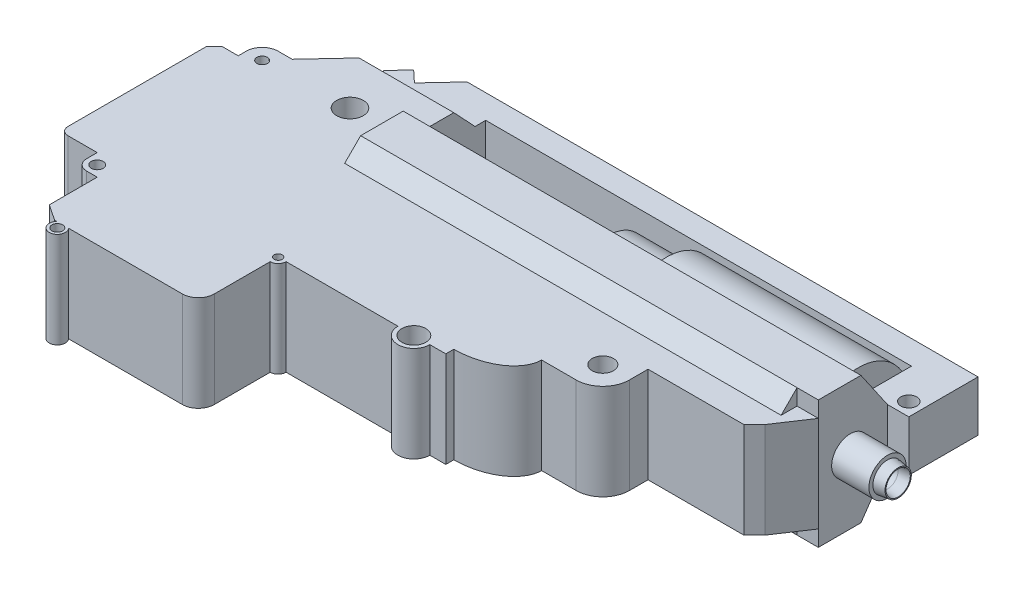
SolidWorks part; units mm, degrees
ref_plane "Alzado" through (0, 0, 0) normal (0, 0, 1) x (1, 0, 0)
ref_plane "Planta" through (0, 0, 0) normal (0, 1, 0) x (1, 0, 0)
ref_plane "Vista lateral" through (0, 0, 0) normal (1, 0, 0) x (0, 0, -1)
sketch "Croquis1" plane through (0, 0, 0) normal (0, 1, 0) x (1, 0, 0)
  line L0 (0, 0) -> (96, 0)
  line L1 (96, 0) -> (96, -13)
  line L2 (0, 0) -> (-4.2707, -4.5758)
  line L3 (96, -13) -> (88, -13)
  line L4 (96, -13) -> (96, -10.5)
  line L5 (96, -10.5) -> (93.5, -10.5)
  line L6 (88, -4.5) -> (88, -13)
  line L7 (88, -4.5) -> (8, -4.5)
  line L8 (88, -13) -> (87.902, -13.0151)
  line L9 (8, -4.5) -> (8, -7.5)
  line L10 (8, -7.5) -> (-7, -7.5)
  line L11 (-7, -7.5) -> (-9.9242, -4.7707)
  line L12 (-9.9242, -4.7707) -> (-7.1949, -1.8465)
  line L13 (-7.1949, -1.8465) -> (-4.2707, -4.5758)
  line L14 (-7, -7.5) -> (-10.4116, -11.1553) construction
  line L15 (-13.3358, -8.426) -> (-10.4116, -11.1553)
  line L16 (-13.1409, -14.0795) -> (-16.0651, -11.3502)
  line L17 (-16.0651, -11.3502) -> (-13.3358, -8.426)
  line L18 (-13.1409, -14.0795) -> (-10.4116, -11.1553)
  circle A0 centre (93.5, -10.5) radius 1.5
  dimension "D7" = 3
  dimension "D1" = 96
  dimension "D2" = 13
  dimension "D3" = 15
  dimension "D4" = 8
  dimension "D5" = 2.5
  dimension "D6" = 2.5
  dimension "D8" = 80
  dimension "D9" = 4
  dimension "D10" = 4
  dimension "D11" = 5
extrude "Saliente-Extruir1" add sketch "Croquis1" along normal blind 9.5 contours A0 L1 L0 L2 L10 L9 L7 L6 L3 | L16 L18 L15 L17 region at (46.9477, 0, 3.2955) region at (-13.2383, 0, 11.2528)
sketch "Croquis2" plane through (88, 0, 0) normal (-1, 0, 0) x (0, 0, 1)
  line L0 (4.5, 4.75) -> (5, 4.75) construction
  line L2 (4.5, 9.5) -> (4.5, 0) construction
  line L3 (5, 4.75) -> (14.5, 4.75) construction
  circle A0 centre (14.5, 4.75) radius 9.5
  dimension "D1" = 0.5
  dimension "D2" = 9.5
extrude "Saliente-Extruir2" add sketch "Croquis2" along normal blind 36
sketch "Croquis3" plane through (52, 0, 0) normal (-1, 0, 0) x (0, 0, 1)
  circle A0 centre (14.5, 4.75) radius 7.5
  dimension "D1" = 15
extrude "Saliente-Extruir3" add sketch "Croquis3" along normal blind 11
sketch "Croquis5" plane through (41, 0, 0) normal (-1, 0, 0) x (0, 0, 1)
  circle A0 centre (14.5, 4.75) radius 3.5
  dimension "D1" = 7
extrude "Saliente-Extruir4" add sketch "Croquis5" along normal blind 33
sketch "Croquis6" plane through (88, 0, 0) normal (1, 0, 0) x (0, 0, -1)
  line L0 (-13, 4.75) -> (-26, 4.75) construction
  line L1 (-13, 9.5) -> (-13, 0) construction
  line L2 (-26, -7.25) -> (-26, 16.75)
  line L3 (-26, 16.75) -> (-18, 16.75)
  line L4 (-18, 16.75) -> (-13, 9.5)
  line L5 (-13, 9.5) -> (-13, 0)
  line L6 (-18, -7.25) -> (-13, 0)
  line L7 (-26, -7.25) -> (-18, -7.25)
  dimension "D1" = 13
  dimension "D2" = 12
  dimension "D3" = 8
extrude "Saliente-Extruir5" add sketch "Croquis6" along normal blind 4
sketch "Croquis7" plane through (92, 0, 0) normal (1, 0, 0) x (0, 0, -1)
  line L0 (-13, 4.75) -> (-20, 4.75) construction
  line L1 (-13, 0) -> (-13, 9.5) construction
  circle A0 centre (-20, 4.75) radius 3.5
  circle A1 centre (-20, 4.75) radius 2
  dimension "D2" = 7
  dimension "D3" = 4
  dimension "D1" = 7
extrude "Saliente-Extruir6" add sketch "Croquis7" along normal blind 7
sketch "Croquis8" plane through (99, 0, 0) normal (1, 0, 0) x (0, 0, -1)
  circle A0 centre (-20, 4.75) radius 2
  circle A1 centre (-20, 4.75) radius 2.75
  dimension "D1" = 5.5
extrude "Saliente-Extruir7" add sketch "Croquis8" along normal blind 2 draft 8
sketch "Croquis9" plane through (8, 0, 0) normal (-1, 0, 0) x (0, 0, 1)
  line L10 (6.5, 9.5) -> (10.5, 13.75)
  line L13 (4.5, 4.75) -> (17.5, 4.75) construction
  line L14 (10.5, 13.75) -> (17.5, 13.75)
  line L15 (17.5, -4.25) -> (17.5, 13.75)
  line L18 (4.5, 0) -> (4.5, 9.5)
  line L19 (4.5, 0) -> (6.5, 0)
  line L20 (4.5, 9.5) -> (10.5, 9.5) construction
  line L21 (17.5, -4.25) -> (10.5, -4.25)
  line L22 (4.5, 9.5) -> (6.5, 9.5)
  line L23 (10.5, 9.5) -> (10.5, 13.75) construction
  line L24 (6.5, 0) -> (10.5, -4.25)
  dimension "D3" = 13
  dimension "D6" = 2
  dimension "D7" = 6
extrude "Saliente-Extruir8" add sketch "Croquis9" along normal blind 23
sketch "Croquis17" plane through (0, 13.75, 0) normal (0, 1, 0) x (1, 0, 0)
  line L0 (0, 0) -> (-16.8, -18)
  line L1 (-16.8, -18) -> (-16.7852, -17.9144)
  line L4 (0, 0) -> (-16.8, 0)
  line L5 (-16.8, 0) -> (-16.8, -18)
  line M3 (8, -10.5) -> (-15, -10.5)
  line M4 (-15, -10.5) -> (-15, -17.5)
extrude "Cortar-Extruir3" cut sketch "Croquis17" along normal blind 40 and the other way blind 34 contours L4 L5 L0 M4 M3 | L0 M3 M4 region at (-10.981, 13.75, 5.3264) region at (-13.2667, 13.75, 12.3571)
sketch "Croquis18" plane through (88, 0, 0) normal (-1, 0, 0) x (0, 0, 1)
  line L0 (18, -7.25) -> (26, -7.25)
  line L1 (26, 16.75) -> (26, -7.25) construction
  line L2 (26, 16.75) -> (18, 16.75)
  line L3 (18, 16.75) -> (18, 13.75)
  line L4 (18, 13.75) -> (26, 13.75)
  line L5 (26, 13.75) -> (29, 13.75)
  line L6 (26, 16.75) -> (29, 13.75)
  line L7 (26, -4.25) -> (29, -4.25)
  line L8 (18, -7.25) -> (18, -4.25)
  line L9 (18, -4.25) -> (26, -4.25)
  line L10 (29, -4.25) -> (26, -7.25)
  dimension "D1" = 3
  dimension "D2" = 3
extrude "Saliente-Extruir10" add sketch "Croquis18" along normal blind 82
sketch "Croquis19" plane through (0, 13.75, 0) normal (0, 1, 0) x (1, 0, 0)
  line L0 (8, -17.5) -> (8, -24.5)
  line L1 (8, -24.5) -> (-26, -24.5)
  line L2 (-26, -24.5) -> (-26, -23)
  line L3 (-26, -23) -> (-24.5, -23) construction
  line L4 (-24.5, -23) -> (-24.5, -21.5) construction
  line L5 (-26, -23) -> (-24.5, -21.5)
  line L6 (-24.5, -21.5) -> (-21.5, -21.5)
  line L7 (-21.5, -21.5) -> (-18.5, -21.5) construction
  line L8 (-18.5, -21.5) -> (-18.5, -20) construction
  line L9 (-18.5, -20) -> (-18.5, -17) construction
  line L10 (-18.5, -17) -> (-16.8667, -17)
  line L11 (8, -17.5) -> (-15, -17.5)
  line L12 (-15, -16.0714) -> (-15.8667, -17)
  line L13 (-15, -16.0714) -> (-15, -17.5)
  line L14 (-21.5, -21.5) -> (-21.5, -20)
  line L15 (-16.8667, -17) -> (-15.8667, -17)
  line L16 (0, 0) -> (0, -19.5) construction
  line L17 (0, -19.5) -> (-2.5, -19.5) construction
  line L20 (-9.8, -10.5) -> (-15, -16.0714)
  line L21 (-15, -16.0714) -> (-15, -17.5)
  line L22 (-15, -17.5) -> (8, -17.5)
  line L23 (8, -17.5) -> (8, -10.5)
  line L24 (8, -10.5) -> (-9.8, -10.5)
  line L25 (-9.8, -10.5) -> (-12.4, -13.2857)
  line L27 (-15, -17.5) -> (8, -17.5)
  line L28 (8, -17.5) -> (8, -10.5)
  line L29 (8, -10.5) -> (-9.8, -10.5)
  arc A0 (-18.5, -17) -> (-21.5, -20) centre (-18.5, -20) ccw
  circle A1 centre (-18.5, -20) radius 1
  line M11 (-15, -16.0714) -> (-15, -17.5)
  line M12 (-15, -17.5) -> (8, -17.5)
  dimension "D11" = 2
  dimension "D1" = 7
  dimension "D2" = 34
  dimension "D3" = 1.5
  dimension "D4" = 1.5
  dimension "D5" = 1.5
  dimension "D6" = 3
  dimension "D7" = 3
  dimension "D8" = 1.5
  dimension "D9" = 3
  dimension "D12" = 19.5
  dimension "D13" = 2.5
  dimension "D10" = 0
extrude "Saliente-Extruir11" add sketch "Croquis19" against normal blind 18 contours L10 A0 L14 L6 L5 L2 L1 L0 M12 M11 region at (-7.6013, 13.75, 21.099)
sketch "Croquis20" plane through (0, 13.75, 0) normal (0, 1, 0) x (1, 0, 0)
  line L0 (0, 0) -> (0, -19.5) construction
  line L1 (0, -19.5) -> (-2.5, -19.5) construction
  circle A0 centre (-2.5, -19.5) radius 2.5
  dimension "D1" = 19.5
  dimension "D2" = 2.5
extrude "Cortar-Extruir4" cut sketch "Croquis20" against normal blind 18
sketch "Croquis21" plane through (0, 13.75, 0) normal (0, 1, 0) x (1, 0, 0)
  line L0 (-26, -24.5) -> (-26, -49)
  line L1 (-24.5, -50.5) -> (-19, -50.5)
  line L2 (-26, -24.5) -> (6, -24.5)
  line L4 (-19, -50.5) -> (-19, -52.5)
  line L5 (-15, -54.5) -> (-15, -63.5)
  line L6 (-15, -63.5) -> (-12, -63.5) construction
  line L7 (-12, -63.5) -> (-12, -65.5) construction
  line L8 (-15, -63.5) -> (-12, -65.5)
  line L9 (-12, -65.5) -> (-11.618, -65.5)
  line L10 (-12, -65.5) -> (-11.618, -65.5)
  line L11 (15, -62.5) -> (15, -52)
  line L12 (-9.382, -65.5) -> (12, -65.5)
  line L14 (16.5, -50.5) -> (37.5, -50.5)
  line L15 (43.5, -50.5) -> (46.5, -50.5)
  line L16 (46.5, -50.5) -> (46.5, -49)
  line L19 (92, -26) -> (88, -32)
  line L20 (88, -32) -> (86, -32) construction
  line L21 (86, -32) -> (86, -34) construction
  line L22 (88, -32) -> (86, -34)
  line L23 (86, -34) -> (68, -34)
  line L24 (96, 0) -> (96, -37.5) construction
  line L25 (-17, -54.5) -> (-15, -54.5)
  line L26 (96, -37.5) -> (63, -37.5) construction
  line L27 (68, -34) -> (68, -37.5)
  line L28 (63, 0) -> (63, -40) construction
  line L29 (0, 0) -> (96, 0) construction
  line L30 (63, -42.5) -> (56.5, -42.5)
  line L31 (6, -24.5) -> (92, -24.5)
  line L32 (92, -18) -> (92, -26) construction
  line L33 (92, -24.5) -> (92, -26)
  arc A0 (-19, -52.5) -> (-17, -54.5) centre (-17, -52.5) ccw
  arc A1 (-11.618, -65.5) -> (-9.382, -65.5) centre (-10.5, -66.5) ccw
  arc A2 (12, -65.5) -> (15, -62.5) centre (12, -62.5) ccw
  arc A3 (15, -52) -> (16.5, -50.5) centre (15, -50.5) ccw
  arc A4 (37.5, -50.5) -> (43.5, -50.5) centre (40.5, -50.5) ccw
  circle A5 centre (63, -37.5) radius 2
  arc A6 (63, -42.5) -> (68, -37.5) centre (63, -37.5) ccw
  circle A7 centre (-10.5, -66.5) radius 0.9991
  circle A8 centre (40.5, -50.5) radius 2.25
  circle A9 centre (15, -50.5) radius 0.75
  circle A10 centre (-17, -52.5) radius 1.1246
  arc A11 (-24.5, -50.5) -> (-26, -49) centre (-24.5, -49) cw
  ellipse E0 centre (46.5, -42.5) end of major axis (56.5, -42.5) minor radius 6.5 (46.5, -49) -> (56.5, -42.5) ccw
  point P57 (-26, -50.5)
  line M13 (-26, -24.5) -> (6, -24.5)
  dimension "D5" = 4
  dimension "D12" = 3
  dimension "D11" = 3
  dimension "D23" = 4
  dimension "D3" = 4.5
  dimension "D4" = 1.5
  dimension "D6" = 1.5
  dimension "D1" = 26
  dimension "D2" = 7
  dimension "D7" = 3
  dimension "D8" = 2
  dimension "D9" = 24
  dimension "D10" = 12
  dimension "D13" = 21
  dimension "D14" = 6
  dimension "D15" = 3
  dimension "D16" = 1.5
  dimension "D18" = 2
  dimension "D19" = 2
  dimension "D20" = 18
  dimension "D21" = 37.5
  dimension "D22" = 33
  dimension "D24" = 40
  dimension "D25" = 6.5
extrude "Saliente-Extruir19" add sketch "Croquis21" against normal blind 18 contours L16 E0 L30 A6 L27 L23 L22 L19 L33 L31 L0 L1 L4 A0 L25 L5 L8 L9 A1 L12 A2 L11 A3 L14 A4 L15 A5 M13 region at (19.8463, 13.75, 39.6627)
sketch "Croquis22" plane through (0, 9.5, 0) normal (0, 1, 0) x (1, 0, 0)
  line L0 (0, 0) -> (-4.7762, -5.1174) construction
  line L1 (0, 0) -> (-6.0667, -6.5) construction
  line L2 (-4.7762, -5.1174) -> (-6.9694, -3.0704)
  line L3 (-4.7762, -5.1174) -> (-7.5055, -8.0416)
  line L4 (-9.8, -10.5) -> (-6.0667, -6.5) construction
  line L5 (-7.5055, -8.0416) -> (-9.6987, -5.9947)
  line L6 (-9.6987, -5.9947) -> (-6.9694, -3.0704)
  line L7 (-7.5055, -8.0416) -> (-10.2348, -10.9658) construction
  line L8 (-15.8667, -17) -> (-9.8, -10.5) construction
  line L9 (-10.2348, -10.9658) -> (-12.4279, -8.9189)
  line L10 (-12.4279, -8.9189) -> (-15.1572, -11.8431)
  line L11 (-15.1572, -11.8431) -> (-12.964, -13.8901)
  line L12 (-10.2348, -10.9658) -> (-12.964, -13.8901)
  dimension "D1" = 7
  dimension "D2" = 3
  dimension "D3" = 4
  dimension "D4" = 3
  dimension "D5" = 4
  dimension "D6" = 4
extrude "Saliente-Extruir20" add sketch "Croquis22" against normal blind 9.5
